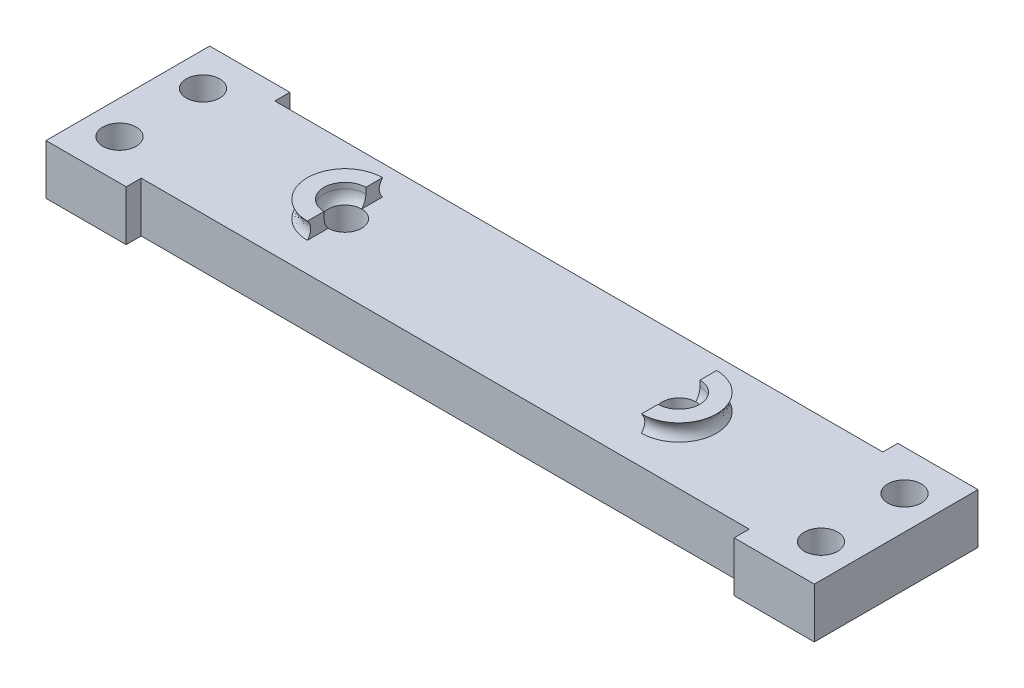
SolidWorks part; units mm, degrees
ref_plane "前视基准面" through (0, 0, 0) normal (0, 0, 1) x (1, 0, 0)
ref_plane "上视基准面" through (0, 0, 0) normal (0, 1, 0) x (1, 0, 0)
ref_plane "右视基准面" through (0, 0, 0) normal (1, 0, 0) x (0, 0, -1)
sketch "草图1" plane through (0, 0, 0) normal (0, 1, 0) x (1, 0, 0)
  line L0 (-24.9943, 0) -> (11.0057, 0)
  line L1 (11.0057, 0) -> (11.0057, 1)
  line L2 (-24.9943, 1) -> (-29.9943, 1)
  line L3 (-29.9943, 1) -> (-29.9943, -9)
  line L4 (-29.9943, -9) -> (-24.9943, -9)
  line L5 (11.0057, -9) -> (11.0057, -8)
  line L6 (11.0057, -8) -> (-24.9943, -8)
  line L7 (-24.9943, -8) -> (-24.9943, -9)
  line L8 (11.0057, -9) -> (16.0057, -9)
  line L9 (16.0057, -9) -> (16.0057, 1)
  line L10 (16.0057, 1) -> (11.0057, 1)
  line L11 (-24.9943, 1) -> (-24.9943, 0)
  circle A0 centre (-27.9943, -6.5) radius 1
  circle A1 centre (-27.9943, -1.5) radius 1
  circle A2 centre (14.0057, -1.5) radius 1
  circle A3 centre (14.0057, -6.5) radius 1
  dimension "D5" = 2
  dimension "D6" = 2
  dimension "D11" = 2
  dimension "D12" = 2
  dimension "D1" = 8
  dimension "D2" = 36
  dimension "D3" = 36
  dimension "D7" = 1
  dimension "D8" = 1
  dimension "D9" = 1
  dimension "D10" = 1
  dimension "D13" = 42
extrude "凸台-拉伸2" add sketch "草图1" along normal blind 4
sketch "草图2" plane through (0, 4, 0) normal (0, 1, 0) x (1, 0, 0)
  line L5 (-14.8943, -4) -> (0.9057, -4) construction
  line L6 (-14.8943, -1.75) -> (0.9057, -1.75)
  line L7 (-14.8943, -6.25) -> (0.9057, -6.25)
  arc A2 (-14.8943, -1.75) -> (-14.8943, -6.25) centre (-14.8943, -4) ccw
  arc A3 (0.9057, -6.25) -> (0.9057, -1.75) centre (0.9057, -4) ccw
  point P11 (-6.9943, -4)
  dimension "D5" = 2.25
extrude "凸台-拉伸3" add sketch "草图2" along normal blind 1
sketch "草图3" plane through (0, 5, 0) normal (0, 1, 0) x (1, 0, 0)
  line L1 (0.9057, -1.75) -> (-14.8943, -1.75) construction
  line L5 (-14.8943, -2.5) -> (-14.8943, -1.75)
  line L6 (-14.8943, -1.75) -> (0.9057, -1.75)
  line L7 (0.9057, -1.75) -> (0.9057, -2.5)
  line L8 (-14.8943, -5.5) -> (-14.8943, -6.25)
  line L9 (-14.8943, -6.25) -> (0.9057, -6.25)
  line L10 (0.9057, -6.25) -> (0.9057, -5.5)
  arc A0 (0.9057, -5.5) -> (0.9057, -2.5) centre (0.9057, -4) ccw
  arc A1 (-14.8943, -5.5) -> (-14.8943, -2.5) centre (-14.8943, -4) cw
  dimension "D3" = 1.5
  dimension "D4" = 1.5
extrude "切除-拉伸2" cut sketch "草图3" against normal blind 1
sketch "草图4" plane through (-14.8943, 0, 0) normal (1, 0, 0) x (0, 0, -1)
  line L0 (-6.25, 5) -> (-6.25, 4)
  spline S0 degree 2 poles (-6.25, 5) (-5.95, 4.5) (-6.25, 4) knots 0 0 0 1 1 1
sketch "草图5" plane through (0, 5, 0) normal (0, 1, 0) x (1, 0, 0)
  circle A0 centre (-14.8943, -4) radius 2.25
sweep "切除-扫描2" cut profiles "草图4" path "草图5"
sketch "草图8" plane through (0.9057, 0, 0) normal (-1, 0, 0) x (0, 0, 1)
  line L0 (6.25, 4) -> (6.25, 5)
  spline S0 degree 2 poles (6.25, 4) (5.95, 4.5) (6.25, 5) knots 0 0 0 1 1 1
sketch "草图9" plane through (0, 5, 0) normal (0, 1, 0) x (1, 0, 0)
  circle A0 centre (0.9057, -4) radius 2.25
sweep "切除-扫描3" cut profiles "草图8" path "草图9"
sketch "草图10" plane through (0, 0, 0) normal (0, -1, 0) x (1, 0, 0)
  circle A0 centre (-6.9943, 4.2405) radius 25.3994
extrude "切除-拉伸3" cut sketch "草图10" against normal blind 3
sketch "草图11" plane through (0, 4, 0) normal (0, 1, 0) x (1, 0, 0)
  circle A0 centre (-7.8727, -3.5616) radius 29.4361
extrude "切除-拉伸4" cut sketch "草图11" along normal blind 10
sketch "草图12" plane through (0, 4, 0) normal (0, 1, 0) x (1, 0, 0)
  line L5 (-16.9943, -1.75) -> (-16.9943, -2.75)
  line L6 (-16.9943, -6.25) -> (-16.9943, -5.25)
  line L7 (3.0057, -1.75) -> (3.0057, -2.75)
  line L8 (3.0057, -5.25) -> (3.0057, -6.25)
  arc A0 (-16.9943, -1.75) -> (-16.9943, -6.25) centre (-16.9943, -4) ccw
  arc A1 (3.0057, -1.75) -> (3.0057, -6.25) centre (3.0057, -4) cw
  arc A2 (-16.9943, -2.75) -> (-16.9943, -5.25) centre (-16.9943, -4) ccw
  arc A3 (3.0057, -2.75) -> (3.0057, -5.25) centre (3.0057, -4) cw
  dimension "D3" = 2.25
  dimension "D4" = 2.25
  dimension "D5" = 1.25
  dimension "D6" = 1.25
extrude "凸台-拉伸4" add sketch "草图12" along normal blind 1
sketch "草图13" plane through (-16.9943, 0, 0) normal (1, 0, 0) x (0, 0, -1)
  line L2 (-1.75, 5) -> (-1.75, 4)
  spline S0 degree 2 poles (-1.75, 5) (-2.15, 4.5) (-1.75, 4) knots 0 0 0 1 1 1
sketch "草图14" plane through (0, 5, 0) normal (0, 1, 0) x (1, 0, 0)
  circle A0 centre (-16.9943, -4) radius 2.25
sweep "切除-扫描4" cut profiles "草图13" path "草图14"
sketch "草图15" plane through (3.0057, 0, 0) normal (-1, 0, 0) x (0, 0, 1)
  line L2 (1.75, 5) -> (1.75, 4)
  spline S0 degree 2 poles (1.75, 5) (2.15, 4.5) (1.75, 4) knots 0 0 0 1 1 1
sketch "草图16" plane through (0, 5, 0) normal (0, 1, 0) x (1, 0, 0)
  circle A0 centre (3.0057, -4) radius 2.25
sweep "切除-扫描5" cut profiles "草图15" path "草图16"
sketch "草图17" plane through (0, 3, 0) normal (0, -1, 0) x (1, 0, 0)
  line L0 (-24.9943, 8) -> (-24.9943, 9)
  line L1 (-24.9943, 8) -> (-25.1943, 8)
  line L2 (-24.9943, 9) -> (-25.1943, 9)
  line L3 (-25.1943, 8) -> (-25.1943, 9)
  line L4 (-24.9943, 0) -> (-24.9943, -1)
  line L5 (-24.9943, 0) -> (-25.1943, 0)
  line L6 (-24.9943, -1) -> (-25.1943, -1)
  line L7 (-25.1943, 0) -> (-25.1943, -1)
  line L8 (11.0057, 9) -> (11.0057, 8)
  line L9 (11.0057, 9) -> (11.2057, 9)
  line L10 (11.0057, 8) -> (11.2057, 8)
  line L11 (11.2057, 9) -> (11.2057, 8)
  line L12 (11.0057, -1) -> (11.0057, 0)
  line L13 (11.0057, -1) -> (11.2057, -1)
  line L14 (11.0057, 0) -> (11.2057, 0)
  line L15 (11.2057, -1) -> (11.2057, 0)
  dimension "D1" = 0.2
  dimension "D2" = 0.2
  dimension "D3" = 0.2
  dimension "D4" = 0.2
extrude "切除-拉伸6" cut sketch "草图17" against normal blind 4
sketch "草图18" plane through (0, 3, 0) normal (0, -1, 0) x (1, 0, 0)
  line L0 (16.0057, 9) -> (11.2057, 9)
  line L1 (16.0057, 9) -> (16.0057, 8.9)
  line L2 (11.2057, 9) -> (11.2057, 8.9)
  line L3 (16.0057, 8.9) -> (11.2057, 8.9)
  line L4 (11.2057, -1) -> (16.0057, -1)
  line L5 (11.2057, -1) -> (11.2057, -0.9)
  line L6 (16.0057, -1) -> (16.0057, -0.9)
  line L7 (11.2057, -0.9) -> (16.0057, -0.9)
  line L8 (-29.9943, 9) -> (-25.1943, 9)
  line L9 (-29.9943, 9) -> (-29.9943, 8.9)
  line L10 (-25.1943, 9) -> (-25.1943, 8.9)
  line L11 (-29.9943, 8.9) -> (-25.1943, 8.9)
  line L12 (-25.1943, -1) -> (-29.9943, -1)
  line L13 (-25.1943, -1) -> (-25.1943, -0.9)
  line L14 (-29.9943, -1) -> (-29.9943, -0.9)
  line L15 (-25.1943, -0.9) -> (-29.9943, -0.9)
  dimension "D1" = 0.1
  dimension "D2" = 0.1
  dimension "D3" = 0.1
  dimension "D4" = 0.1
extrude "切除-拉伸7" cut sketch "草图18" against normal blind 4
sketch "草图19" plane through (0, 4, 0) normal (0, 1, 0) x (1, 0, 0)
  circle A0 centre (3.0057, -4) radius 1
  circle A2 centre (-16.9943, -4) radius 1
  dimension "D1" = 2
  dimension "D2" = 2
extrude "切除-拉伸8" cut sketch "草图19" against normal blind 4
fillet "圆角1" radius 1 1 edges at (-18.2443, 4, 4)
fillet "圆角2" radius 1 1 edges at (4.2557, 4, 4)
sketch "草图21" plane through (0, 3, 0) normal (0, -1, 0) x (1, 0, 0)
  line L0 (-29.9943, 8.9) -> (-25.1943, 8.9)
  line L1 (-25.1943, 8.9) -> (-25.1943, 8)
  line L2 (-25.1943, 8) -> (11.2057, 8)
  line L3 (11.2057, 8) -> (11.2057, 8.9)
  line L4 (11.2057, 8.9) -> (16.0057, 8.9)
  line L5 (16.0057, 8.9) -> (16.0057, -0.9)
  line L6 (16.0057, -0.9) -> (11.2057, -0.9)
  line L7 (11.2057, -0.9) -> (11.2057, 0)
  line L8 (11.2057, 0) -> (-25.1943, 0)
  line L9 (-25.1943, 0) -> (-25.1943, -0.9)
  line L10 (-25.1943, -0.9) -> (-29.9943, -0.9)
  line L11 (-29.9943, -0.9) -> (-29.9943, 8.9)
  circle A0 centre (-27.9943, 6.5) radius 1
  circle A1 centre (-27.9943, 1.5) radius 1
  circle A2 centre (-16.9943, 4) radius 1
  circle A3 centre (3.0057, 4) radius 1
  circle A4 centre (14.0057, 6.5) radius 1
  circle A5 centre (14.0057, 1.5) radius 1
extrude "凸台-拉伸5" add sketch "草图21" along normal blind 2
